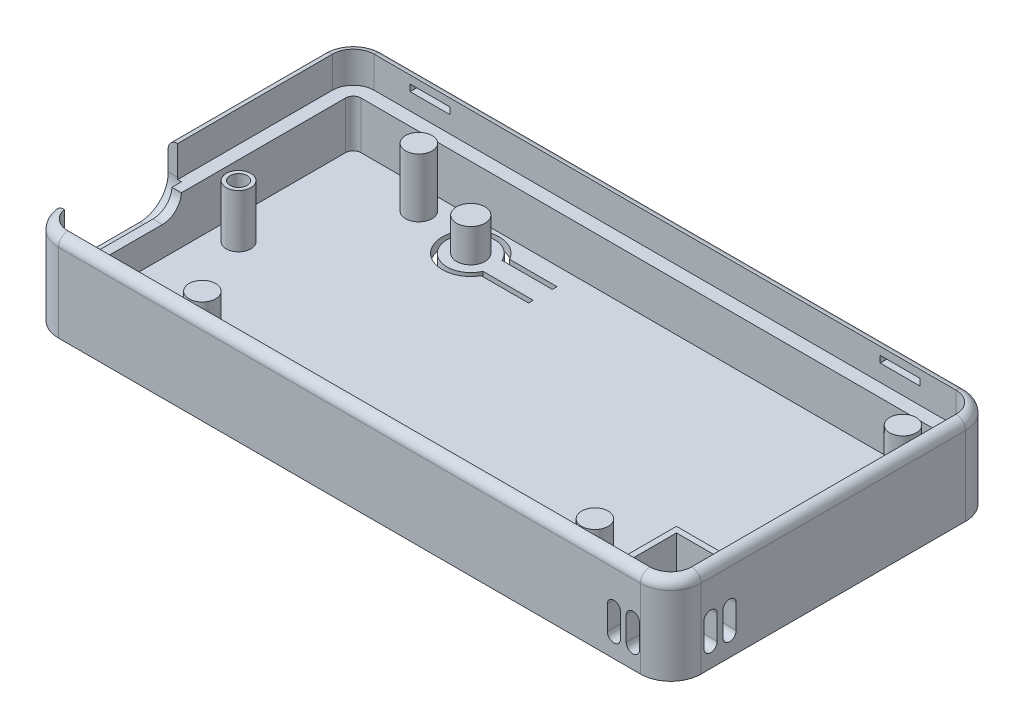
SolidWorks part; units mm, degrees
ref_plane "前视基准面" through (0, 0, 0) normal (0, 0, 1) x (1, 0, 0)
ref_plane "上视基准面" through (0, 0, 0) normal (0, 1, 0) x (1, 0, 0)
ref_plane "右视基准面" through (0, 0, 0) normal (1, 0, 0) x (0, 0, -1)
other "Configuration Table"
sketch "草图1" plane through (0, 0, 0) normal (0, 1, 0) x (1, 0, 0)
  line L1 (-30.7, 17.15) -> (30.7, 17.15)
  line L2 (-33.9, 13.95) -> (-33.9, -13.95)
  line L3 (-30.7, -17.15) -> (30.7, -17.15)
  line L4 (33.9, 13.95) -> (33.9, -13.95)
  line L5 (-33.9, 17.15) -> (33.9, -17.15) construction
  line L6 (-33.9, -17.15) -> (33.9, 17.15) construction
  arc A0 (30.7, 17.15) -> (33.9, 13.95) centre (30.7, 13.95) cw
  arc A1 (30.7, -17.15) -> (33.9, -13.95) centre (30.7, -13.95) ccw
  arc A2 (-33.9, -13.95) -> (-30.7, -17.15) centre (-30.7, -13.95) ccw
  arc A3 (-30.7, 17.15) -> (-33.9, 13.95) centre (-30.7, 13.95) ccw
  point P0 (0, 0)
  dimension "D3" = 3.2
  dimension "D1" = 67.8
  dimension "D2" = 34.3
extrude "凸台-拉伸1" add sketch "草图1" along normal blind 9.3
sketch "草图2" plane through (0, 9.3, 0) normal (0, 1, 0) x (1, 0, 0)
  line L8 (32.9, -13.95) -> (32.9, 13.95)
  line L9 (-30.7, -16.15) -> (30.7, -16.15)
  line L10 (-32.9, 13.95) -> (-32.9, -13.95)
  line L11 (30.7, 16.15) -> (-30.7, 16.15)
  line L12 (32.9, -13.95) -> (32.9, 13.95)
  line L13 (-30.7, -16.15) -> (30.7, -16.15)
  line L14 (-32.9, 13.95) -> (-32.9, -13.95)
  line L15 (30.7, 16.15) -> (-30.7, 16.15)
  arc A8 (32.9, 13.95) -> (30.7, 16.15) centre (30.7, 13.95) ccw
  arc A9 (30.7, -16.15) -> (32.9, -13.95) centre (30.7, -13.95) ccw
  arc A10 (-32.9, -13.95) -> (-30.7, -16.15) centre (-30.7, -13.95) ccw
  arc A11 (-30.7, 16.15) -> (-32.9, 13.95) centre (-30.7, 13.95) ccw
  arc A12 (32.9, 13.95) -> (30.7, 16.15) centre (30.7, 13.95) ccw
  arc A13 (30.7, -16.15) -> (32.9, -13.95) centre (30.7, -13.95) ccw
  arc A14 (-32.9, -13.95) -> (-30.7, -16.15) centre (-30.7, -13.95) ccw
  arc A15 (-30.7, 16.15) -> (-32.9, 13.95) centre (-30.7, 13.95) ccw
  dimension "D1" = 1
extrude "切除-拉伸1" cut sketch "草图2" against normal blind 3.3
sketch "草图3" plane through (0, 6, 0) normal (0, 1, 0) x (1, 0, 0)
  line L25 (31.5, -13.95) -> (31.5, 13.95)
  line L26 (-30.7, -14.75) -> (30.7, -14.75)
  line L27 (-31.5, 13.95) -> (-31.5, -13.95)
  line L28 (30.7, 14.75) -> (-30.7, 14.75)
  line L29 (31.5, -13.95) -> (31.5, 13.95)
  line L30 (-30.7, -14.75) -> (30.7, -14.75)
  line L31 (-31.5, 13.95) -> (-31.5, -13.95)
  line L32 (30.7, 14.75) -> (-30.7, 14.75)
  arc A4 (31.5, 13.95) -> (30.7, 14.75) centre (30.7, 13.95) ccw
  arc A5 (31.5, 13.95) -> (30.7, 14.75) centre (30.7, 13.95) ccw
  arc A6 (30.7, -14.75) -> (31.5, -13.95) centre (30.7, -13.95) ccw
  arc A7 (30.7, -14.75) -> (31.5, -13.95) centre (30.7, -13.95) ccw
  arc A8 (-31.5, -13.95) -> (-30.7, -14.75) centre (-30.7, -13.95) ccw
  arc A9 (-31.5, -13.95) -> (-30.7, -14.75) centre (-30.7, -13.95) ccw
  arc A10 (-30.7, 14.75) -> (-31.5, 13.95) centre (-30.7, 13.95) ccw
  arc A11 (-30.7, 14.75) -> (-31.5, 13.95) centre (-30.7, 13.95) ccw
  dimension "D1" = 1.4
extrude "切除-拉伸2" cut sketch "草图3" against normal offset from surface (5 mm away) 1 up to face at (0, 0, 0)
ref_plane "基准面1" through (0, 0, 0) normal (1, 0, 0) x (0, 0, -1)
sketch "草图5" plane through (0, 0, 16.15) normal (0, 0, -1) x (-1, 0, 0)
  line L1 (-26.9, 8.47) -> (-22.7, 8.47)
  line L2 (-26.9, 8.47) -> (-26.9, 7.77)
  line L3 (-26.9, 7.77) -> (-22.7, 7.77)
  line L4 (-22.7, 8.47) -> (-22.7, 7.77)
  line L5 (-32.9, 6) -> (-32.9, 9.3) construction
  line L6 (30.7, 6) -> (-30.7, 6) construction
  line L7 (0, 6.8747) -> (0, -6.8747) construction
  line L8 (26.9, 7.77) -> (22.7, 7.77)
  line L9 (22.7, 8.47) -> (22.7, 7.77)
  line L10 (26.9, 8.47) -> (22.7, 8.47)
  line L11 (26.9, 8.47) -> (26.9, 7.77)
  dimension "D1" = 4.2
  dimension "D2" = 0.7
  dimension "D3" = 10.2
  dimension "D4" = 1.77
extrude "切除-拉伸4" cut sketch "草图5" against normal blind 0.7
fillet "圆角8" radius 0.5 2 edges at (-24.8, 8.47, 16.85) (24.8, 8.47, 16.85)
mirror "镜向2" about plane through (0, 0, 0) normal (0, 0, 1) of "圆角8", "切除-拉伸4"
fillet "圆角4" radius 1 8 edges at (32.9627, 9.3, -16.2127) (0, 9.3, -17.15) (-32.9627, 9.3, -16.2127) (-33.9, 9.3, 0) (-32.9627, 9.3, 16.2127) (0, 9.3, 17.15) (32.9627, 9.3, 16.2127) (33.9, 9.3, 0)
sketch "草图8" plane through (0, 1, 0) normal (0, 1, 0) x (1, 0, 0)
  line L0 (26.3, -14.75) -> (26.3, -8.95)
  line L1 (-30.7, -14.75) -> (30.7, -14.75) construction
  line L2 (26.3, -8.95) -> (31.5, -8.95)
  line L3 (31.5, -13.95) -> (31.5, 13.95) construction
  line L4 (31.5, -8.95) -> (31.5, -9.55)
  line L5 (31.5, -9.55) -> (26.9, -9.55)
  line L6 (26.9, -9.55) -> (26.9, -14.75)
  line L7 (26.9, -14.75) -> (26.3, -14.75)
  dimension "D1" = 0.6
  dimension "D2" = 5.2
  dimension "D3" = 4.6
extrude "凸台-拉伸2" add sketch "草图8" along normal blind 6.2
sketch "草图9" plane through (0, 1, 0) normal (0, 1, 0) x (1, 0, 0)
  line L1 (-13.1019, 12.85) -> (-8.1019, 12.85)
  line L3 (-13.4087, 12.35) -> (-8.1019, 12.35)
  line L4 (-8.1019, 12.85) -> (-8.1019, 12.35)
  line L5 (-13.4087, 10.35) -> (-8.1019, 10.35)
  line L7 (-13.1019, 9.85) -> (-8.1019, 9.85)
  line L8 (-8.1019, 10.35) -> (-8.1019, 9.85)
  line L9 (30.7, 14.75) -> (-30.7, 14.75) construction
  line L10 (-31.5, 13.95) -> (-31.5, -13.95) construction
  arc A0 (-13.1019, 12.85) -> (-13.1019, 9.85) centre (-15.7, 11.35) ccw
  arc A1 (-13.4087, 12.35) -> (-13.4087, 10.35) centre (-15.7, 11.35) ccw
  dimension "D1" = 0.5
  dimension "D5" = 2.5
  dimension "D2" = 0.5
  dimension "D3" = 1
  dimension "D4" = 1
  dimension "D6" = 5
  dimension "D7" = 15.8
  dimension "D8" = 3.4
extrude "切除-拉伸6" cut sketch "草图9" against normal through all
sketch "草图10" plane through (0, 1, 0) normal (0, 1, 0) x (1, 0, 0)
  circle A0 centre (-15.7, 11.35) radius 1.5
  dimension "D1" = 3
extrude "凸台-拉伸3" add sketch "草图10" along normal blind 3.5
sketch "草图11" plane through (-31.5, 0, 0) normal (1, 0, 0) x (0, 0, -1)
  line L0 (-11.38, 6.1) -> (-5.38, 6.1) construction
  line L1 (-11.38, 8.1) -> (-5.38, 8.1)
  line L2 (-11.38, 4.1) -> (-5.38, 4.1)
  line L3 (13.95, 6) -> (-13.95, 6) construction
  line L5 (-14.75, 1) -> (-14.75, 6) construction
  arc A0 (-11.38, 8.1) -> (-11.38, 4.1) centre (-11.38, 6.1) ccw
  arc A1 (-5.38, 4.1) -> (-5.38, 8.1) centre (-5.38, 6.1) ccw
  point P2 (-8.38, 6.1)
  dimension "D2" = 6
  dimension "D1" = 4
  dimension "D3" = 0.1
  dimension "D4" = 6.37
extrude "切除-拉伸7" cut sketch "草图11" against normal blind 3
sketch "草图12" plane through (0, 1, 0) normal (0, 1, 0) x (1, 0, 0)
  line L0 (-31.5, 13.95) -> (-31.5, -13.95) construction
  line L1 (-30.7, -14.75) -> (26.3, -14.75) construction
  circle A0 centre (-29, 0.15) radius 1.3
  dimension "D2" = 2.6
  dimension "D1" = 2.5
  dimension "D3" = 14.9
extrude "凸台-拉伸4" add sketch "草图12" along normal blind 5.6
sketch "草图13" plane through (-33.9, 0, 0) normal (-1, 0, 0) x (0, 0, 1)
  line L5 (11.38, 9.1) -> (5.38, 9.1)
  line L6 (5.38, 3.1) -> (11.38, 3.1)
  line L7 (11.38, 9.1) -> (5.38, 9.1)
  line L8 (5.38, 3.1) -> (11.38, 3.1)
  arc A6 (11.38, 3.1) -> (11.38, 9.1) centre (11.38, 6.1) ccw
  arc A7 (5.38, 9.1) -> (5.38, 3.1) centre (5.38, 6.1) ccw
  arc A8 (11.38, 3.1) -> (11.38, 9.1) centre (11.38, 6.1) ccw
  arc A9 (5.38, 9.1) -> (5.38, 3.1) centre (5.38, 6.1) ccw
  dimension "D1" = 1
extrude "切除-拉伸8" cut sketch "草图13" against normal blind 1.4
sketch "草图14" plane through (-33.9, 0, 0) normal (-1, 0, 0) x (0, 0, 1)
  line L0 (13.3775, 6) -> (14.3783, 6) construction
  line L6 (14.3783, 6) -> (2.3817, 6)
  line L7 (14.3783, 6) -> (14.3783, 9.3)
  line L8 (14.3783, 9.3) -> (2.3817, 9.3)
  line L9 (2.3817, 6) -> (2.3817, 9.3)
  line L10 (-13.95, 9.3) -> (13.95, 9.3) construction
  arc A7 (3.3404, 8.3) -> (5.38, 3.1) centre (5.38, 6.1) ccw construction
extrude "切除-拉伸9" cut sketch "草图14" against normal blind 6.6
sketch "草图15" plane through (0, 6.6, 0) normal (0, 1, 0) x (1, 0, 0)
  circle A0 centre (-29, 0.15) radius 0.9
  circle A1 centre (-29, 0.15) radius 1.3 construction
  dimension "D1" = 0.4
extrude "切除-拉伸10" cut sketch "草图15" against normal through all
sketch "草图16" plane through (0, 1, 0) normal (0, 1, 0) x (1, 0, 0)
  line L0 (-30.7, -14.75) -> (26.3, -14.75) construction
  line L1 (31.5, -8.95) -> (31.5, 13.95) construction
  line L2 (31.5, -8.95) -> (31.5, 13.95) construction
  line L5 (30.7, 14.75) -> (-30.7, 14.75) construction
  line L6 (30.7, 14.75) -> (-30.7, 14.75) construction
  line L7 (-31.5, 13.95) -> (-31.5, -3.3825) construction
  line L8 (-31.5, 13.95) -> (-31.5, -13.95) construction
  circle A0 centre (29, 12.25) radius 1.4
  circle A1 centre (-20.2, -12.47) radius 1.4
  circle A2 centre (21.3, -12.55) radius 1.4
  circle A3 centre (-22.3, 12.47) radius 1.4
  dimension "D1" = 2.8
  dimension "D2" = 2.2
  dimension "D3" = 10.2
  dimension "D4" = 2.5
  dimension "D5" = 2.5
  dimension "D6" = 2.28
  dimension "D7" = 9.2
  dimension "D8" = 11.3
  dimension "D9" = 2.28
extrude "凸台-拉伸5" add sketch "草图16" along normal blind 6.2
sketch "草图4" plane through (-32.9, 0, 0) normal (1, 0, 0) x (0, 0, -1)
  line L1 (-2.1, 8.47) -> (2.1, 8.47)
  line L2 (-2.1, 8.47) -> (-2.1, 7.77)
  line L3 (-2.1, 7.77) -> (2.1, 7.77)
  line L4 (2.1, 8.47) -> (2.1, 7.77)
  line L5 (-16.15, 6) -> (-16.15, 9.3) construction
  line L6 (13.95, 6) -> (-2.3817, 6) construction
  dimension "D1" = 4.2
  dimension "D2" = 0.7
  dimension "D3" = 14.05
  dimension "D4" = 1.77
sketch "草图18" plane through (32.9, 0, 0) normal (-1, 0, 0) x (0, 0, 1)
  line L0 (2.1, 7.77) -> (-2.1, 7.77) construction
  line L1 (2.1, 8.47) -> (2.1, 7.77) construction
  line L2 (2.1, 8.47) -> (-2.1, 8.47) construction
  line L3 (-2.1, 8.47) -> (-2.1, 7.77) construction
  line L4 (2.1, 7.77) -> (-2.1, 7.77)
  line L5 (2.1, 8.47) -> (2.1, 7.77)
  line L6 (2.1, 8.47) -> (-2.1, 8.47)
  line L7 (-2.1, 8.47) -> (-2.1, 7.77)
extrude "切除-拉伸11" cut sketch "草图18" against normal blind 0.7
sketch "草图19" plane through (31.5, 0, 0) normal (-1, 0, 0) x (0, 0, 1)
  line L0 (10.95, 4.65) -> (10.95, 2.15) construction
  line L1 (11.65, 4.65) -> (11.65, 2.15)
  line L2 (10.25, 4.65) -> (10.25, 2.15)
  line L5 (9.55, 1) -> (9.55, 6) construction
  line L6 (13.95, 1) -> (9.55, 1) construction
  line L7 (12.95, 4.65) -> (12.95, 2.15) construction
  line L8 (13.65, 4.65) -> (13.65, 2.15)
  line L9 (12.25, 4.65) -> (12.25, 2.15)
  arc A0 (11.65, 4.65) -> (10.25, 4.65) centre (10.95, 4.65) ccw
  arc A1 (10.25, 2.15) -> (11.65, 2.15) centre (10.95, 2.15) ccw
  arc A2 (13.65, 4.65) -> (12.25, 4.65) centre (12.95, 4.65) ccw
  arc A3 (12.25, 2.15) -> (13.65, 2.15) centre (12.95, 2.15) ccw
  point P2 (10.95, 3.4)
  point P14 (12.95, 3.4)
  dimension "D1" = 0.7
  dimension "D2" = 2.5
  dimension "D3" = 1.4
  dimension "D4" = 2.4
  dimension "D6" = 2
  dimension "D5" = 2
extrude "切除-拉伸12" cut sketch "草图19" against normal through all
sketch "草图20" plane through (0, 0, 14.75) normal (0, 0, -1) x (-1, 0, 0)
  line L0 (-27.9, 4.65) -> (-27.9, 2.15) construction
  line L1 (-27.2, 4.65) -> (-27.2, 2.15)
  line L2 (-28.6, 4.65) -> (-28.6, 2.15)
  line L3 (-29.9, 4.65) -> (-29.9, 2.15) construction
  line L4 (-26.9, 1) -> (-30.7, 1) construction
  line L5 (-26.9, 6) -> (-26.9, 1) construction
  line L6 (-29.2, 4.65) -> (-29.2, 2.15)
  line L7 (-30.6, 4.65) -> (-30.6, 2.15)
  arc A0 (-27.2, 4.65) -> (-28.6, 4.65) centre (-27.9, 4.65) ccw
  arc A1 (-28.6, 2.15) -> (-27.2, 2.15) centre (-27.9, 2.15) ccw
  arc A2 (-29.2, 4.65) -> (-30.6, 4.65) centre (-29.9, 4.65) ccw
  arc A3 (-30.6, 2.15) -> (-29.2, 2.15) centre (-29.9, 2.15) ccw
  point P2 (-27.9, 3.4)
  point P14 (-29.9, 3.4)
  dimension "D1" = 0.7
  dimension "D2" = 2.5
  dimension "D3" = 2.4
  dimension "D4" = 1
  dimension "D6" = 2
  dimension "D5" = 2
extrude "切除-拉伸13" cut sketch "草图20" against normal through all
sketch "草图21" plane through (0, 1, 0) normal (0, 1, 0) x (1, 0, 0)
  line L0 (28.2, -11.15) -> (28.2, -13.15) construction
  line L1 (28.9, -11.15) -> (28.9, -13.15)
  line L2 (27.5, -11.15) -> (27.5, -13.15)
  line L3 (26.9, -9.55) -> (31.5, -9.55) construction
  line L4 (26.9, -14.75) -> (26.9, -9.55) construction
  line L5 (30.2, -11.15) -> (30.2, -13.15) construction
  line L6 (30.9, -11.15) -> (30.9, -13.15)
  line L7 (29.5, -11.15) -> (29.5, -13.15)
  arc A0 (28.9, -11.15) -> (27.5, -11.15) centre (28.2, -11.15) ccw
  arc A1 (27.5, -13.15) -> (28.9, -13.15) centre (28.2, -13.15) ccw
  arc A2 (30.9, -11.15) -> (29.5, -11.15) centre (30.2, -11.15) ccw
  arc A3 (29.5, -13.15) -> (30.9, -13.15) centre (30.2, -13.15) ccw
  point P2 (28.2, -12.15)
  point P15 (30.2, -12.15)
  dimension "D1" = 0.7
  dimension "D2" = 2.6
  dimension "D3" = 2
  dimension "D4" = 1.3
  dimension "D6" = 2
  dimension "D5" = 2
extrude "切除-拉伸14" cut sketch "草图21" against normal through all
